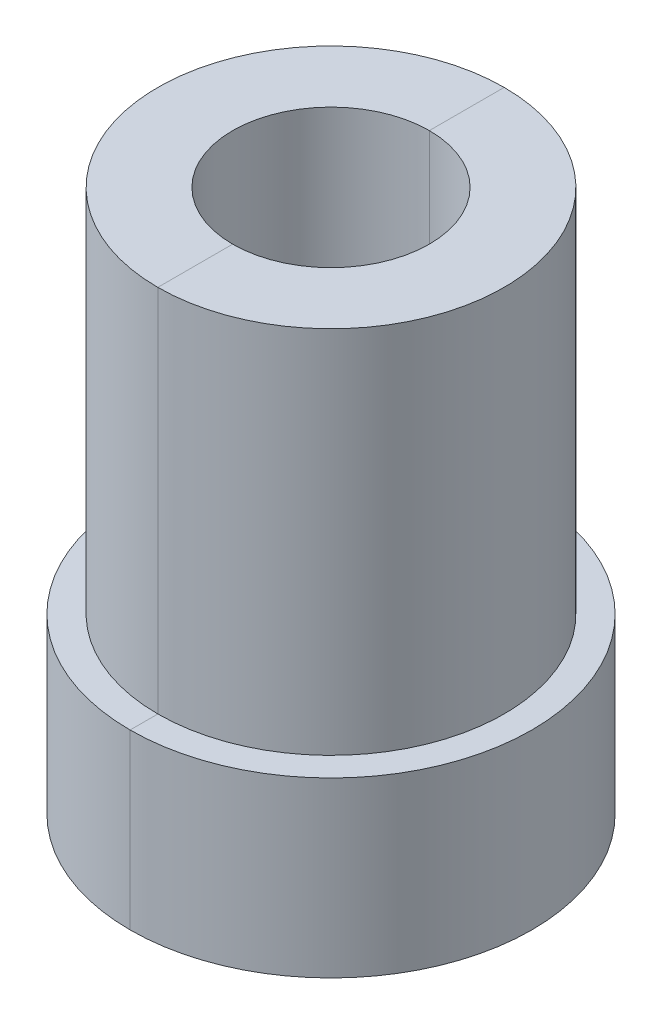
SolidWorks part; units mm, degrees
ref_plane "Front Plane" through (0, 0, 0) normal (0, 0, 1) x (1, 0, 0)
ref_plane "Top Plane" through (0, 0, 0) normal (0, 1, 0) x (1, 0, 0)
ref_plane "Right Plane" through (0, 0, 0) normal (1, 0, 0) x (0, 0, -1)
sketch "Sketch1" plane through (0, 0, 0) normal (0, 1, 0) x (1, 0, 0)
  circle A0 centre (0, 0) radius 5.5245
  dimension "D1" = 11.049
extrude "Boss-Extrude1" add sketch "Sketch1" along normal blind 4.7625
sketch "Sketch2" plane through (0, 4.7625, 0) normal (0, 1, 0) x (1, 0, 0)
  circle A0 centre (0, 0) radius 4.7625
  dimension "D1" = 9.525
extrude "Boss-Extrude2" add sketch "Sketch2" along normal blind 10.16
sketch "Sketch3" plane through (0, 14.9225, 0) normal (0, 1, 0) x (1, 0, 0)
  circle A0 centre (0, 0) radius 2.7051
  dimension "D1" = 5.4102
extrude "Cut-Extrude1" cut sketch "Sketch3" against normal through all
split line "Split Line1"
